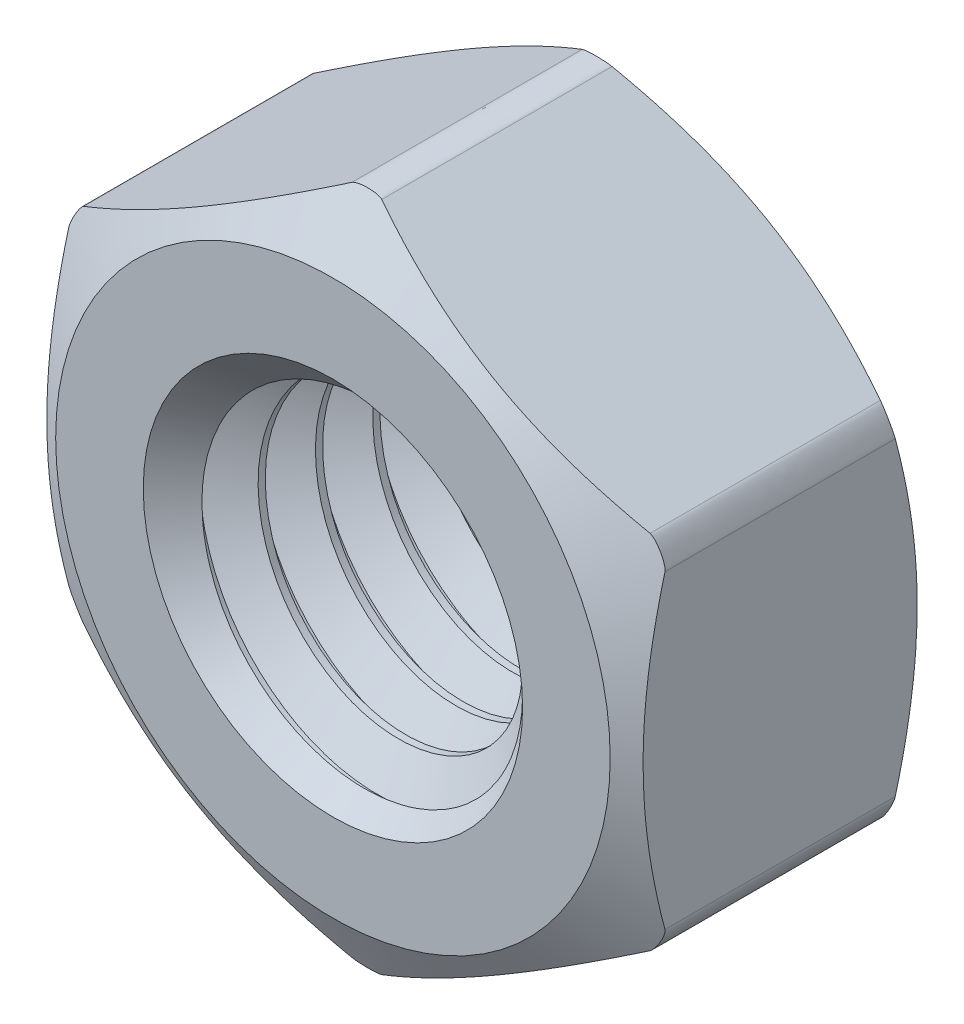
SolidWorks part; units mm, degrees
ref_plane "Front Plane" through (0, 0, 0) normal (0, 0, 1) x (1, 0, 0)
ref_plane "Top Plane" through (0, 0, 0) normal (0, 1, 0) x (1, 0, 0)
ref_plane "Right Plane" through (0, 0, 0) normal (1, 0, 0) x (0, 0, -1)
sketch "Sketch1" plane through (0, 0, 0) normal (0, 0, 1) x (1, 0, 0)
  line L0 (0, -7.5056) -> (0, 7.5056) construction
  line L1 (0, -7.5056) -> (6.5, -3.7528) construction
  line L2 (6.5, -3.7528) -> (6.5, 3.7528) construction
  line L3 (6.5, 3.7528) -> (0, 7.5056) construction
  line L4 (0, 7.5056) -> (-6.5, 3.7528) construction
  line L5 (-6.5, 3.7528) -> (-6.5, -3.7528) construction
  line L6 (-6.5, -3.7528) -> (0, -7.5056) construction
  line L7 (-6.5, 0) -> (6.5, 0) construction
  line L8 (0, 0) -> (-2, -3.4641) construction
  circle A0 centre (0, 0) radius 6.5 construction
  circle A1 centre (0, 0) radius 4 construction
  point P11 (0, 0)
  point P12 (0, -4)
  point P14 (4, 0)
  point P15 (0, 4)
  point P16 (-4, 0)
  point P19 (-2, -3.4641)
  dimension "Thread Diameter" = 8
  dimension "Width" = 13
  dimension "D1" = 30
sketch "Sketch2" plane through (0, 0, 0) normal (1, 0, 0) x (0, 0, -1)
  line L0 (0, -6.5) -> (0, 6.5) construction
  line L1 (-3.25, 6.5) -> (3.25, 6.5) construction
  line L2 (-3.25, 6.5) -> (-3.25, -6.5) construction
  line L3 (-3.25, -6.5) -> (3.25, -6.5) construction
  line L4 (3.25, 6.5) -> (3.25, -6.5) construction
  line L5 (3.25, 0) -> (-3.25, 0) construction
  line L8 (-3.25, 4) -> (3.25, 4) construction
  line L9 (-3.25, -4) -> (3.25, -4) construction
  line L10 (-4.4219, 4.1353) -> (-3.1719, 4.1353) construction
  line L11 (-3.1719, 4.1353) -> (-3.7969, 3.0528) construction
  line L12 (-3.7969, 3.0528) -> (-4.4219, 4.1353) construction
  line L13 (-4.3828, 4.0677) -> (-3.2109, 4.0677) construction
  line L14 (-4.3438, 4) -> (-3.25, 4) construction
  line L15 (-3.875, 3.1881) -> (-3.7188, 3.1881) construction
  line L16 (-3.7969, 3.1881) -> (-3.7969, 3.0528) construction
  line L17 (-3.7969, 4.1353) -> (-3.7969, 4) construction
  point P8 (0, 0)
  point P29 (-3.7969, 4.0677)
  dimension "Height" = 6.5
  dimension "Thread Pitch" = 1.25
  dimension "D2" = 0.1562
sketch "Sketch3" plane through (0, 0, 0) normal (0, 0, 1) x (1, 0, 0)
  line L1 (0, -7.5056) -> (6.5, -3.7528)
  line L2 (6.5, -3.7528) -> (6.5, 3.7528)
  line L3 (6.5, 3.7528) -> (0, 7.5056)
  line L4 (0, 7.5056) -> (-6.5, 3.7528)
  line L5 (-6.5, 3.7528) -> (-6.5, -3.7528)
  line L6 (-6.5, -3.7528) -> (0, -7.5056)
  circle A0 centre (0, 0) radius 6.5 construction
  circle A1 centre (0, 0) radius 3.1881
extrude "Boss-Extrude1" add sketch "Sketch3" along normal up to vertex (3.25 mm away) and the other way up to vertex (3.25 mm away) up to point (0, 0, 3.25) other way up to point (0, 0, -3.25)
sketch "Sketch4" plane through (0, 0, 0) normal (0, 0, 1) x (1, 0, 0)
  circle A0 centre (0, 0) radius 6.045
  dimension "D1" = 12.09
extrude "Cut-Extrude1" cut sketch "Sketch4" against normal through all draft 60 from vertex flip side to cut starting at point (0, 0, 3.25)
extrude "Cut-Extrude2" cut sketch "Sketch4<2>" along normal through all draft 60 from vertex flip side to cut starting at point (0, 0, -3.25)
sketch "Sketch4<2>" plane through (0, 0, 0) normal (0, 0, 1) x (1, 0, 0) same geometry as "Sketch4"
chamfer "Chamfer1" distance 0.7812 angle 45 2 edges at (3.1881, 0, -3.25) (3.1881, 0, 3.25)
fillet "Fillet1" radius 0.65 6 edges at (-6.5, -3.7528, 0) (-6.5, 3.7528, 0) (0, -7.5056, 0) (6.5, -3.7528, 0) (0, 7.5056, 0) (6.5, 3.7528, 0) conic rho 0.25
ref_axis "Center Axis 1" through (0, 0, -21.8476) along (0, 0, 1)
sketch "Sketch5" plane through (0, 0, 0) normal (0, 0, 1) x (1, 0, 0)
  circle A0 centre (0, 0) radius 4 construction
  circle A1 centre (0, 0) radius 4
extrude "Cut-Extrude3" cut sketch "Sketch5" against normal through all both and the other way through all
sketch "Sketch6" plane through (0, 0, 3.25) normal (0, 0, 1) x (1, 0, 0)
  circle A0 centre (0, 0) radius 4 construction
  circle A1 centre (0, 0) radius 4
curve "Helix/Spiral1" pitch 1.25 height 7.75 radius 4 centre (0, 0, 3.25) axis (0, 0, -1) start towards (0, 1, 0)
sketch "Sketch7" plane through (0, 0, 0) normal (1, 0, 0) x (0, 0, -1)
  line L0 (-4.3828, 4.0677) -> (-3.2109, 4.0677)
  line L1 (-3.2109, 4.0677) -> (-3.7188, 3.1881)
  line L2 (-3.7188, 3.1881) -> (-3.875, 3.1881)
  line L3 (-3.875, 3.1881) -> (-4.3828, 4.0677)
sweep "Sweep1" add profiles "Sketch7" path "Helix/Spiral1"
sketch "Sketch8" plane through (0, 0, 3.25) normal (0, 0, 1) x (1, 0, 0)
  circle A0 centre (0, 0) radius 4.1353
extrude "Cut-Extrude4" cut sketch "Sketch8" against normal through all draft 45 and the other way through all
sketch "Sketch9" plane through (0, 0, -3.25) normal (0, 0, -1) x (-1, 0, 0)
  circle A1 centre (0, 0) radius 4.1353
  circle A2 centre (0, 0) radius 4.1353
  dimension "D1" = 0
extrude "Cut-Extrude5" cut sketch "Sketch9" against normal through all draft 45 and the other way through all
equation "\"D2@Sketch2\" = \"Thread Pitch@Sketch2\" / 8"
equation "\"D1@Chamfer1\"=\"Thread Pitch@Sketch2\"*.625"
equation "\"D1@Sketch4\"=\"Width@Sketch1\"*.93"
equation "\"D1@Fillet1\"=\"Width@Sketch1\"*.05"
equation "\"D4@Helix/Spiral1\"=\"Thread Pitch@Sketch2\""
equation "\"D3@Helix/Spiral1\"=\"Height@Sketch2\"+\"Thread Pitch@Sketch2\""
